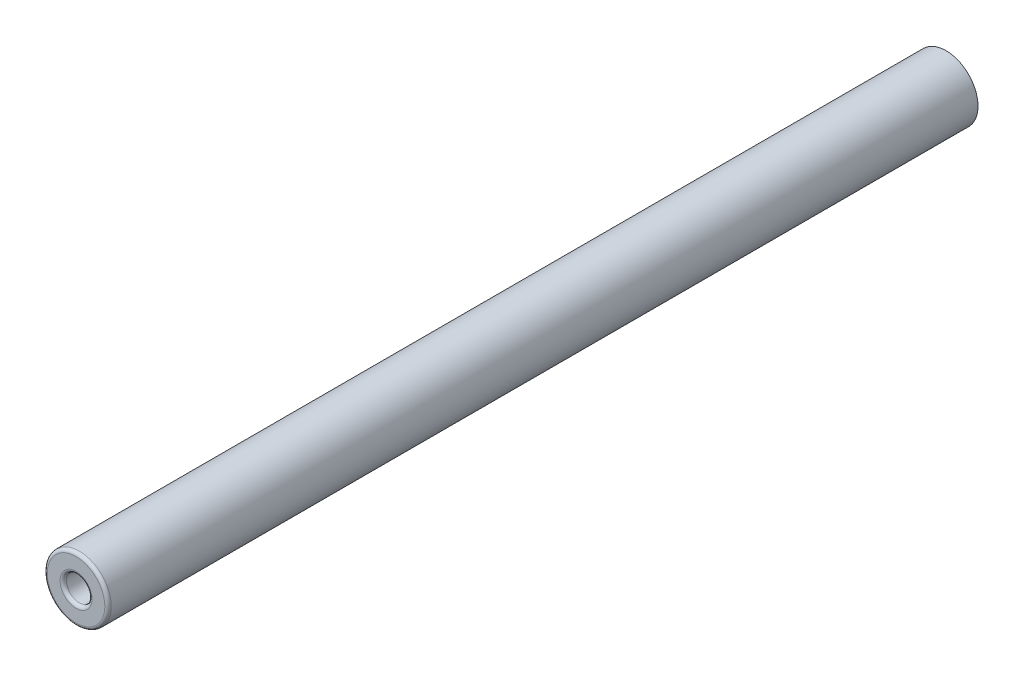
SolidWorks part; units mm, degrees
ref_plane "Front Plane" through (0, 0, 0) normal (0, 0, 1) x (1, 0, 0)
ref_plane "Top Plane" through (0, 0, 0) normal (0, 1, 0) x (1, 0, 0)
ref_plane "Right Plane" through (0, 0, 0) normal (1, 0, 0) x (0, 0, -1)
sketch "Sketch1" plane through (0, 0, 0) normal (0, 0, 1) x (1, 0, 0)
  circle A0 centre (0, 0) radius 2.5
  dimension "D1" = 5
extrude "Boss-Extrude1" add sketch "Sketch1" along normal mid plane 68
sketch "Sketch2" plane through (0, 0, 34) normal (0, 0, 1) x (1, 0, 0)
  circle A0 centre (0, 0) radius 1
  dimension "D1" = 2
extrude "Cut-Extrude1" cut sketch "Sketch2" against normal blind 20
fillet "Fillet1" radius 0.25 2 edges at (2.5, 0, 34) (1, 0, 34)
